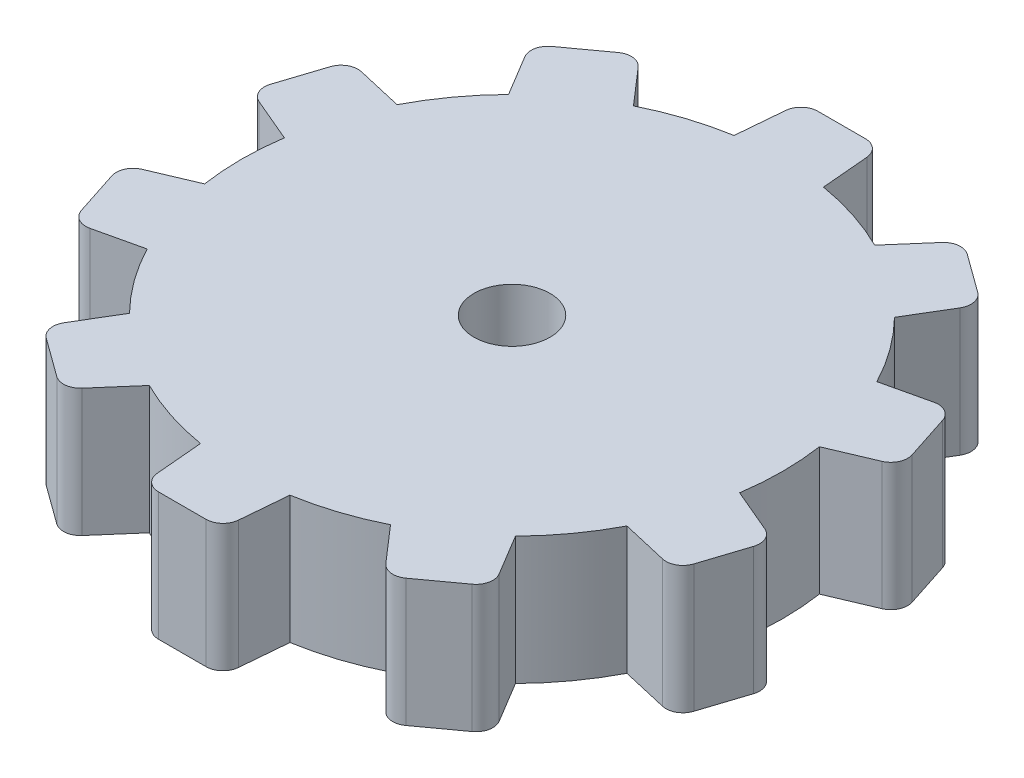
SolidWorks part; units mm, degrees
ref_plane "Front Plane" through (0, 0, 0) normal (0, 0, 1) x (1, 0, 0)
ref_plane "Top Plane" through (0, 0, 0) normal (0, 1, 0) x (1, 0, 0)
ref_plane "Right Plane" through (0, 0, 0) normal (1, 0, 0) x (0, 0, -1)
sketch "Sketch1" plane through (0, 0, 0) normal (0, 1, 0) x (1, 0, 0)
  circle A0 centre (0, 0) radius 16
  circle A1 centre (0, 0) radius 2.25
  dimension "D1" = 4.5
  dimension "D2" = 32
extrude "Boss-Extrude1" add sketch "Sketch1" along normal blind 7.55 contours A0 A1 region at (-15.5475, 0, 0)
sketch "Sketch2" plane through (0, 7.55, 0) normal (0, 1, 0) x (1, 0, 0)
  line L0 (0, 0) -> (0, 19.5) construction
  line L1 (-1.4037, 19.5) -> (1.4037, 19.5)
  line L2 (-7.7294, 16) -> (8.7664, 16) construction
  line L3 (-2.3999, 18.5872) -> (-2.6455, 15.7798)
  line L4 (2.3999, 18.5872) -> (2.6455, 15.7798)
  circle A0 centre (0, 0) radius 16 construction
  arc A1 (2.6455, 15.7798) -> (-2.6455, 15.7798) centre (0, 0) ccw
  arc A2 (-2.3999, 18.5872) -> (-1.4037, 19.5) centre (-1.4037, 18.5) cw
  arc A3 (1.4037, 19.5) -> (2.3999, 18.5872) centre (1.4037, 18.5) cw
  point P12 (-2.32, 19.5)
  point P15 (2.32, 19.5)
  dimension "D4" = 1
  dimension "D1" = 3.5
  dimension "D2" = 95
  dimension "D3" = 2.32
extrude "Boss-Extrude2" add sketch "Sketch2" against normal up to surface (7.55 mm away) up to face at (0, 0, 2.25)
pattern_circular "CirPattern1" count 10 over 360 about axis through (0, 7.55, 0) along (0, 1, 0) of "Boss-Extrude2"
